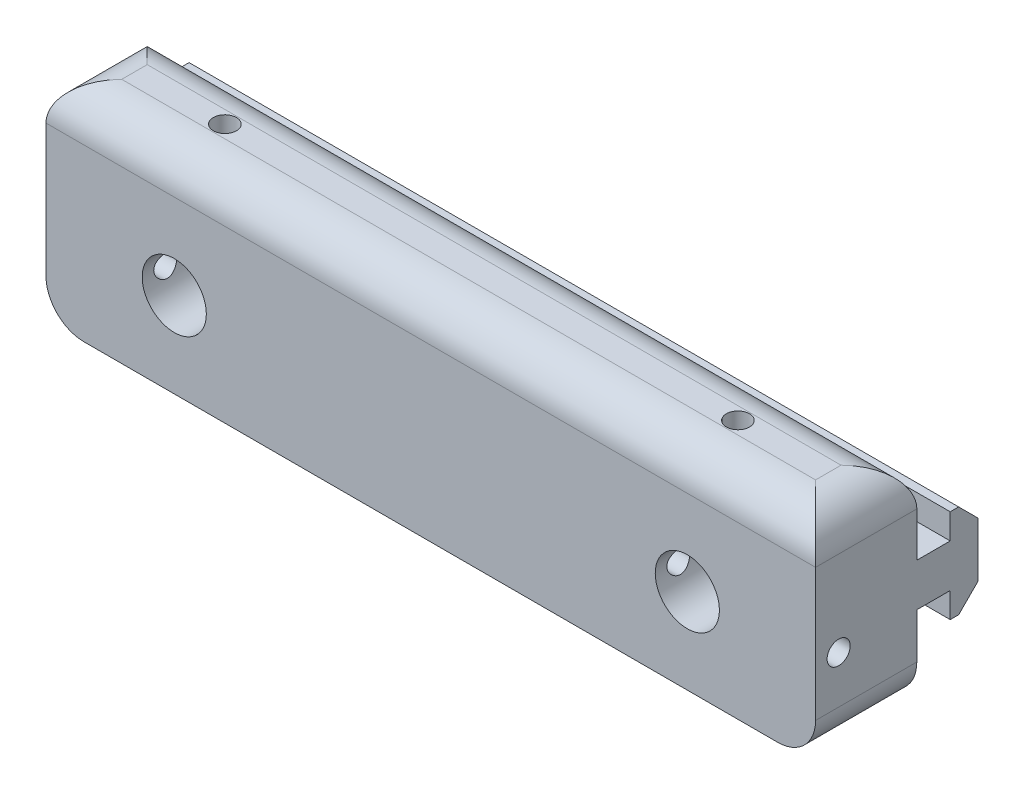
SolidWorks part; units mm, degrees
ref_plane "Front Plane" through (0, 0, 0) normal (0, 0, 1) x (1, 0, 0)
ref_plane "Top Plane" through (0, 0, 0) normal (0, 1, 0) x (1, 0, 0)
ref_plane "Right Plane" through (0, 0, 0) normal (1, 0, 0) x (0, 0, -1)
sketch "Sketch2" plane through (0, 0, 0) normal (1, 0, 0) x (0, 0, -1)
  line L0 (20, -17) -> (20, -5) construction
  line L1 (20, -5) -> (14.5, -5) construction
  line L2 (14.5, -5) -> (14.5, -10) construction
  line L3 (14.5, -10) -> (11.7678, -10) construction
  line L4 (11.7678, -10) -> (7.5, -5.7322) construction
  line L5 (7.5, -5.7322) -> (7.5, -0.5196) construction
  line L6 (7.5, -0.5196) -> (7.2, 0) construction
  line L7 (7.2, 0) -> (7.5, 0.5196) construction
  line L8 (7.5, 0.5196) -> (7.5, 5.7322) construction
  line L9 (7.5, 5.7322) -> (11.7678, 10) construction
  line L10 (11.7678, 10) -> (14.5, 10) construction
  line L11 (14.5, 10) -> (14.5, 5) construction
  line L12 (14.5, 5) -> (20, 5) construction
  line L13 (20, 5) -> (20, 16.9163) construction
  line L14 (17, 19.9163) -> (5, 19.9163) construction
  line L15 (5, 19.9163) -> (5, 14.5) construction
  line L16 (5, 14.5) -> (10, 14.5) construction
  line L17 (10, 14.5) -> (10, 11.7678) construction
  line L18 (10, 11.7678) -> (5.7322, 7.5) construction
  line L19 (5.7322, 7.5) -> (0.5196, 7.5) construction
  line L20 (0.5196, 7.5) -> (0, 7.2) construction
  line L21 (0, 7.2) -> (-0.5196, 7.5) construction
  line L22 (-0.5196, 7.5) -> (-5.7322, 7.5) construction
  line L23 (-5.7322, 7.5) -> (-10, 11.7678) construction
  line L24 (-10, 11.7678) -> (-10, 14.5) construction
  line L25 (-10, 14.5) -> (-5, 14.5) construction
  line L26 (-5, 14.5) -> (-5, 19.9163) construction
  line L27 (-5, 19.9163) -> (-17.0837, 19.9163) construction
  line L28 (-20, 17) -> (-20, 5) construction
  line L29 (-20, 5) -> (-14.5, 5) construction
  line L30 (-14.5, 5) -> (-14.5, 10) construction
  line L31 (-14.5, 10) -> (-11.7678, 10) construction
  line L32 (-11.7678, 10) -> (-7.5, 5.7322) construction
  line L33 (-7.5, 5.7322) -> (-7.5, 0.5196) construction
  line L34 (-7.5, 0.5196) -> (-7.2, 0) construction
  line L35 (-7.2, 0) -> (-7.5, -0.5196) construction
  line L36 (-7.5, -0.5196) -> (-7.5, -5.7322) construction
  line L37 (-7.5, -5.7322) -> (-11.7678, -10) construction
  line L38 (-11.7678, -10) -> (-14.5, -10) construction
  line L39 (-14.5, -10) -> (-14.5, -5) construction
  line L40 (-14.5, -5) -> (-20, -5) construction
  line L41 (-20, -5) -> (-20, -17) construction
  line L42 (-17, -20) -> (17, -20) construction
  line L55 (-21, 3.617) -> (-21, -4.883)
  line L56 (-14.3817, -4.883) -> (-21, -4.883)
  line L57 (-14.3817, -9.883) -> (-14.3817, -4.883)
  line L58 (-12.7101, -9.883) -> (-14.3817, -9.883)
  line L59 (-8.8817, -6.0546) -> (-12.7101, -9.883)
  line L60 (-8.8817, -1.1526) -> (-8.8817, -6.0546)
  line L61 (-8.8817, -0.1134) -> (-8.8817, -1.1526)
  line L62 (-8.8817, 4.7886) -> (-8.8817, -0.1134)
  line L63 (-12.7101, 8.617) -> (-8.8817, 4.7886)
  line L64 (-14.3817, 8.617) -> (-12.7101, 8.617)
  line L65 (-14.3817, 3.617) -> (-14.3817, 8.617)
  line L66 (-21, 3.617) -> (-14.3817, 3.617)
  line L67 (-38.049, -7.3386) -> (-38.049, -11.8386) construction
  line L68 (-37.749, -12.1386) -> (-36.949, -12.1386) construction
  line L69 (-36.949, -12.1386) -> (-36.949, -10.9886) construction
  line L70 (-36.949, -10.9886) -> (-34.349, -10.9886) construction
  line L71 (-34.349, -10.9886) -> (-33.349, -11.9886) construction
  line L72 (-33.349, -11.9886) -> (-33.349, -13.319) construction
  line L73 (-33.349, -13.319) -> (-33.049, -13.8386) construction
  line L74 (-33.049, -13.8386) -> (-33.349, -14.3582) construction
  line L75 (-33.349, -14.3582) -> (-33.349, -15.6886) construction
  line L76 (-33.349, -15.6886) -> (-34.349, -16.6886) construction
  line L77 (-34.349, -16.6886) -> (-36.949, -16.6886) construction
  line L78 (-36.949, -16.6886) -> (-36.949, -15.5386) construction
  line L79 (-36.949, -15.5386) -> (-37.749, -15.5386) construction
  line L80 (-38.049, -15.8386) -> (-38.049, -20.3386) construction
  line L81 (-37.049, -21.3386) -> (-32.549, -21.3386) construction
  line L82 (-32.249, -21.0386) -> (-32.249, -20.2386) construction
  line L83 (-32.249, -20.2386) -> (-33.399, -20.2386) construction
  line L84 (-33.399, -20.2386) -> (-33.399, -17.6386) construction
  line L85 (-33.399, -17.6386) -> (-32.399, -16.6386) construction
  line L86 (-32.399, -16.6386) -> (-31.0686, -16.6386) construction
  line L87 (-31.0686, -16.6386) -> (-30.549, -16.3386) construction
  line L88 (-30.549, -16.3386) -> (-30.0293, -16.6386) construction
  line L89 (-30.0293, -16.6386) -> (-28.699, -16.6386) construction
  line L90 (-28.699, -16.6386) -> (-27.699, -17.6386) construction
  line L91 (-27.699, -17.6386) -> (-27.699, -20.2386) construction
  line L92 (-27.699, -20.2386) -> (-28.849, -20.2386) construction
  line L93 (-28.849, -20.2386) -> (-28.849, -21.0386) construction
  line L94 (-28.549, -21.3386) -> (-24.049, -21.3386) construction
  line L95 (-23.049, -20.3386) -> (-23.049, -15.8386) construction
  line L96 (-23.349, -15.5386) -> (-24.149, -15.5386) construction
  line L97 (-24.149, -15.5386) -> (-24.149, -16.6886) construction
  line L98 (-24.149, -16.6886) -> (-26.749, -16.6886) construction
  line L99 (-26.749, -16.6886) -> (-27.749, -15.6886) construction
  line L100 (-27.749, -15.6886) -> (-27.749, -14.3582) construction
  line L101 (-27.749, -14.3582) -> (-28.049, -13.8386) construction
  line L102 (-28.049, -13.8386) -> (-27.749, -13.319) construction
  line L103 (-27.749, -13.319) -> (-27.749, -11.9886) construction
  line L104 (-27.749, -11.9886) -> (-26.749, -10.9886) construction
  line L105 (-26.749, -10.9886) -> (-24.149, -10.9886) construction
  line L106 (-24.149, -10.9886) -> (-24.149, -12.1386) construction
  line L107 (-24.149, -12.1386) -> (-23.349, -12.1386) construction
  line L108 (-23.049, -11.8386) -> (-23.049, -7.3386) construction
  line L109 (-24.049, -6.3386) -> (-28.549, -6.3386) construction
  line L110 (-28.849, -6.6386) -> (-28.849, -7.4386) construction
  line L111 (-28.849, -7.4386) -> (-27.699, -7.4386) construction
  line L112 (-27.699, -7.4386) -> (-27.699, -10.0386) construction
  line L113 (-27.699, -10.0386) -> (-28.699, -11.0386) construction
  line L114 (-28.699, -11.0386) -> (-30.0293, -11.0386) construction
  line L115 (-30.0293, -11.0386) -> (-30.549, -11.3386) construction
  line L116 (-30.549, -11.3386) -> (-31.0686, -11.0386) construction
  line L117 (-31.0686, -11.0386) -> (-32.399, -11.0386) construction
  line L118 (-32.399, -11.0386) -> (-33.399, -10.0386) construction
  line L119 (-33.399, -10.0386) -> (-33.399, -7.4386) construction
  line L120 (-33.399, -7.4386) -> (-32.249, -7.4386) construction
  line L121 (-32.249, -7.4386) -> (-32.249, -6.6386) construction
  line L122 (-32.549, -6.3386) -> (-37.049, -6.3386) construction
  line L123 (-37.049, -6.3386) -> (-41.049, -6.3386) construction
  line L124 (-24.049, -6.3386) -> (-20.049, -6.3386) construction
  line L125 (-21, 3.617) -> (-21, 19.9163)
  line L126 (-21, 19.9163) -> (-41.049, 19.9163)
  line L127 (-41.049, 19.9163) -> (-41.049, -21.3386)
  line L128 (-41.049, -21.3386) -> (-21, -21.3386)
  line L129 (-21, -21.3386) -> (-21, -5)
  line L130 (-21, -5) -> (-21, 3.617)
  arc A0 (20, 16.9163) -> (17, 19.9163) centre (17, 16.9163) ccw construction
  arc A1 (-17.0837, 19.9163) -> (-20, 17) centre (-17.0837, 17) ccw construction
  arc A2 (-20, -17) -> (-17, -20) centre (-17, -17) ccw construction
  arc A3 (17, -20) -> (20, -17) centre (17, -17) ccw construction
  circle A4 centre (-30.549, -13.8386) radius 1.25 construction
  arc A5 (-38.049, -11.8386) -> (-37.749, -12.1386) centre (-37.749, -11.8386) ccw construction
  arc A6 (-37.749, -15.5386) -> (-38.049, -15.8386) centre (-37.749, -15.8386) ccw construction
  arc A7 (-38.049, -20.3386) -> (-37.049, -21.3386) centre (-37.049, -20.3386) ccw construction
  arc A8 (-32.549, -21.3386) -> (-32.249, -21.0386) centre (-32.549, -21.0386) ccw construction
  arc A9 (-28.849, -21.0386) -> (-28.549, -21.3386) centre (-28.549, -21.0386) ccw construction
  arc A10 (-24.049, -21.3386) -> (-23.049, -20.3386) centre (-24.049, -20.3386) ccw construction
  arc A11 (-23.049, -15.8386) -> (-23.349, -15.5386) centre (-23.349, -15.8386) ccw construction
  arc A12 (-23.349, -12.1386) -> (-23.049, -11.8386) centre (-23.349, -11.8386) ccw construction
  arc A13 (-23.049, -7.3386) -> (-24.049, -6.3386) centre (-24.049, -7.3386) ccw construction
  arc A14 (-28.549, -6.3386) -> (-28.849, -6.6386) centre (-28.549, -6.6386) ccw construction
  arc A15 (-32.249, -6.6386) -> (-32.549, -6.3386) centre (-32.549, -6.6386) ccw construction
  arc A16 (-37.049, -6.3386) -> (-38.049, -7.3386) centre (-37.049, -7.3386) ccw construction
extrude "Boss-Extrude2" add sketch "Sketch2" along normal blind 152.4 contours L129 L130 L55 L125 L126 L127 L128 | L66 L55 L56 L57 L58 L59 L60 L61 L62 L63 L64 L65 region at (0, -0.633, 14.1602) region at (0, -0.7111, 31.0245)
sketch "Sketch3" plane through (0, -21.3386, 0) normal (0, -1, 0) x (1, 0, 0)
  line L56 (56, 37.5197) -> (56, 33.0197) construction
  line L59 (88.9, 41.049) -> (88.9, 21) construction
  line L60 (56.3, 32.7197) -> (57.1, 32.7197) construction
  line L61 (90.9, 38.5197) -> (95.4, 38.5197) construction
  line L62 (57.1, 32.7197) -> (57.1, 33.8697) construction
  line L117 (57.1, 33.8697) -> (59.7, 33.8697) construction
  line L119 (90.6, 37.4197) -> (90.6, 38.2197) construction
  line L120 (59.7, 33.8697) -> (60.7, 32.8697) construction
  line L121 (91.75, 37.4197) -> (90.6, 37.4197) construction
  line L122 (60.7, 32.8697) -> (60.7, 31.5393) construction
  line L290 (60.7, 31.5393) -> (61, 31.0197) construction
  line L291 (61, 31.0197) -> (60.7, 30.5001) construction
  line L292 (60.7, 30.5001) -> (60.7, 29.1697) construction
  line L293 (60.7, 29.1697) -> (59.7, 28.1697) construction
  line L294 (59.7, 28.1697) -> (57.1, 28.1697) construction
  line L295 (57.1, 28.1697) -> (57.1, 29.3197) construction
  line L296 (57.1, 29.3197) -> (56.3, 29.3197) construction
  line L297 (56, 29.0197) -> (56, 24.5197) construction
  line L298 (57, 23.5197) -> (61.5, 23.5197) construction
  line L299 (61.8, 23.8197) -> (61.8, 24.6197) construction
  line L300 (61.8, 24.6197) -> (60.65, 24.6197) construction
  line L301 (60.65, 24.6197) -> (60.65, 27.2197) construction
  line L302 (60.65, 27.2197) -> (61.65, 28.2197) construction
  line L303 (61.65, 28.2197) -> (62.9804, 28.2197) construction
  line L304 (62.9804, 28.2197) -> (63.5, 28.5197) construction
  line L305 (63.5, 28.5197) -> (64.0196, 28.2197) construction
  line L306 (64.0196, 28.2197) -> (65.35, 28.2197) construction
  line L307 (65.35, 28.2197) -> (66.35, 27.2197) construction
  line L308 (66.35, 27.2197) -> (66.35, 24.6197) construction
  line L309 (66.35, 24.6197) -> (65.2, 24.6197) construction
  line L310 (65.2, 24.6197) -> (65.2, 23.8197) construction
  line L311 (65.5, 23.5197) -> (70, 23.5197) construction
  line L312 (71, 24.5197) -> (71, 29.0197) construction
  line L313 (70.7, 29.3197) -> (69.9, 29.3197) construction
  line L314 (69.9, 29.3197) -> (69.9, 28.1697) construction
  line L315 (69.9, 28.1697) -> (67.3, 28.1697) construction
  line L316 (67.3, 28.1697) -> (66.3, 29.1697) construction
  line L317 (66.3, 29.1697) -> (66.3, 30.5001) construction
  line L318 (66.3, 30.5001) -> (66, 31.0197) construction
  line L319 (66, 31.0197) -> (66.3, 31.5393) construction
  line L320 (66.3, 31.5393) -> (66.3, 32.8697) construction
  line L321 (66.3, 32.8697) -> (67.3, 33.8697) construction
  line L322 (67.3, 33.8697) -> (69.9, 33.8697) construction
  line L323 (69.9, 33.8697) -> (69.9, 32.7197) construction
  line L324 (69.9, 32.7197) -> (70.7, 32.7197) construction
  line L325 (71, 33.0197) -> (71, 37.5197) construction
  line L326 (70, 38.5197) -> (65.5, 38.5197) construction
  line L327 (65.2, 38.2197) -> (65.2, 37.4197) construction
  line L328 (65.2, 37.4197) -> (66.35, 37.4197) construction
  line L329 (66.35, 37.4197) -> (66.35, 34.8197) construction
  line L330 (66.35, 34.8197) -> (65.35, 33.8197) construction
  line L331 (65.35, 33.8197) -> (64.0196, 33.8197) construction
  line L332 (64.0196, 33.8197) -> (63.5, 33.5197) construction
  line L333 (63.5, 33.5197) -> (62.9804, 33.8197) construction
  line L334 (62.9804, 33.8197) -> (61.65, 33.8197) construction
  line L335 (61.65, 33.8197) -> (60.65, 34.8197) construction
  line L336 (60.65, 34.8197) -> (60.65, 37.4197) construction
  line L337 (60.65, 37.4197) -> (61.8, 37.4197) construction
  line L338 (61.8, 37.4197) -> (61.8, 38.2197) construction
  line L339 (61.5, 38.5197) -> (57, 38.5197) construction
  line L340 (55.5, 37.4686) -> (55.5, 32.9686)
  line L341 (56.3, 32.1686) -> (57.6, 32.1686)
  line L342 (57.6, 32.1686) -> (57.6, 33.3186)
  line L343 (57.6, 33.3186) -> (59.4929, 33.3186)
  line L344 (59.4929, 33.3186) -> (60.2, 32.6115)
  line L345 (60.2, 32.6115) -> (60.2, 31.3542)
  line L346 (60.2, 31.3542) -> (60.4226, 30.9686)
  line L347 (60.4226, 30.9686) -> (60.2, 30.5829)
  line L348 (60.2, 30.5829) -> (60.2, 29.3257)
  line L349 (60.2, 29.3257) -> (59.4929, 28.6186)
  line L350 (59.4929, 28.6186) -> (57.6, 28.6186)
  line L351 (57.6, 28.6186) -> (57.6, 29.7686)
  line L352 (57.6, 29.7686) -> (56.3, 29.7686)
  line L353 (55.5, 28.9686) -> (55.5, 24.4686)
  line L354 (57, 22.9686) -> (61.5, 22.9686)
  line L355 (62.3, 23.7686) -> (62.3, 25.0686)
  line L356 (62.3, 25.0686) -> (61.15, 25.0686)
  line L357 (61.15, 25.0686) -> (61.15, 26.9615)
  line L358 (61.15, 26.9615) -> (61.8571, 27.6686)
  line L359 (61.8571, 27.6686) -> (63.1144, 27.6686)
  line L360 (63.1144, 27.6686) -> (63.5, 27.8912)
  line L361 (63.5, 27.8912) -> (63.8856, 27.6686)
  line L362 (63.8856, 27.6686) -> (65.1429, 27.6686)
  line L363 (65.1429, 27.6686) -> (65.85, 26.9615)
  line L364 (65.85, 26.9615) -> (65.85, 25.0686)
  line L365 (65.85, 25.0686) -> (64.7, 25.0686)
  line L366 (64.7, 25.0686) -> (64.7, 23.7686)
  line L367 (65.5, 22.9686) -> (70, 22.9686)
  line L368 (71.5, 24.4686) -> (71.5, 28.9686)
  line L369 (70.7, 29.7686) -> (69.4, 29.7686)
  line L370 (69.4, 29.7686) -> (69.4, 28.6186)
  line L371 (69.4, 28.6186) -> (67.5071, 28.6186)
  line L372 (67.5071, 28.6186) -> (66.8, 29.3257)
  line L373 (66.8, 29.3257) -> (66.8, 30.5829)
  line L374 (66.8, 30.5829) -> (66.5774, 30.9686)
  line L375 (66.5774, 30.9686) -> (66.8, 31.3542)
  line L376 (66.8, 31.3542) -> (66.8, 32.6115)
  line L377 (66.8, 32.6115) -> (67.5071, 33.3186)
  line L378 (67.5071, 33.3186) -> (69.4, 33.3186)
  line L379 (69.4, 33.3186) -> (69.4, 32.1686)
  line L380 (69.4, 32.1686) -> (70.7, 32.1686)
  line L381 (71.5, 32.9686) -> (71.5, 37.4686)
  line L382 (70, 38.9686) -> (65.5, 38.9686)
  line L383 (64.7, 38.1686) -> (64.7, 36.8686)
  line L384 (64.7, 36.8686) -> (65.85, 36.8686)
  line L385 (65.85, 36.8686) -> (65.85, 34.9757)
  line L386 (65.85, 34.9757) -> (65.1429, 34.2686)
  line L387 (65.1429, 34.2686) -> (63.8856, 34.2686)
  line L388 (63.8856, 34.2686) -> (63.5, 34.0459)
  line L389 (63.5, 34.0459) -> (63.1144, 34.2686)
  line L390 (63.1144, 34.2686) -> (61.8571, 34.2686)
  line L391 (61.8571, 34.2686) -> (61.15, 34.9757)
  line L392 (61.15, 34.9757) -> (61.15, 36.8686)
  line L393 (61.15, 36.8686) -> (62.3, 36.8686)
  line L394 (62.3, 36.8686) -> (62.3, 38.1686)
  line L395 (61.5, 38.9686) -> (57, 38.9686)
  line L396 (0, 31.0245) -> (152.4, 31.0245) construction
  line L397 (0, 41.049) -> (0, 21) construction
  line L398 (152.4, 41.049) -> (152.4, 21) construction
  line L399 (76.2, 21) -> (76.2, 41.049) construction
  line L400 (152.4, 21) -> (0, 21) construction
  line L401 (152.4, 41.049) -> (0, 41.049) construction
  line L402 (76.2, 41.049) -> (63.5, 41.049) construction
  line L403 (63.5, 41.049) -> (63.5, 21) construction
  line L404 (91.75, 34.8197) -> (91.75, 37.4197) construction
  line L405 (90.75, 33.8197) -> (91.75, 34.8197) construction
  line L406 (89.4196, 33.8197) -> (90.75, 33.8197) construction
  line L407 (88.9, 33.5197) -> (89.4196, 33.8197) construction
  line L408 (88.3804, 33.8197) -> (88.9, 33.5197) construction
  line L409 (87.05, 33.8197) -> (88.3804, 33.8197) construction
  line L410 (86.05, 34.8197) -> (87.05, 33.8197) construction
  line L411 (86.05, 37.4197) -> (86.05, 34.8197) construction
  line L412 (87.2, 37.4197) -> (86.05, 37.4197) construction
  line L413 (87.2, 38.2197) -> (87.2, 37.4197) construction
  line L414 (82.4, 38.5197) -> (86.9, 38.5197) construction
  line L415 (81.4, 33.0197) -> (81.4, 37.5197) construction
  line L416 (82.5, 32.7197) -> (81.7, 32.7197) construction
  line L417 (82.5, 33.8697) -> (82.5, 32.7197) construction
  line L418 (85.1, 33.8697) -> (82.5, 33.8697) construction
  line L419 (86.1, 32.8697) -> (85.1, 33.8697) construction
  line L420 (86.1, 31.5393) -> (86.1, 32.8697) construction
  line L421 (86.4, 31.0197) -> (86.1, 31.5393) construction
  line L422 (86.1, 30.5001) -> (86.4, 31.0197) construction
  line L423 (86.1, 29.1697) -> (86.1, 30.5001) construction
  line L424 (85.1, 28.1697) -> (86.1, 29.1697) construction
  line L425 (82.5, 28.1697) -> (85.1, 28.1697) construction
  line L426 (82.5, 29.3197) -> (82.5, 28.1697) construction
  line L427 (81.7, 29.3197) -> (82.5, 29.3197) construction
  line L428 (81.4, 24.5197) -> (81.4, 29.0197) construction
  line L429 (86.9, 23.5197) -> (82.4, 23.5197) construction
  line L430 (87.2, 24.6197) -> (87.2, 23.8197) construction
  line L431 (86.05, 24.6197) -> (87.2, 24.6197) construction
  line L432 (86.05, 27.2197) -> (86.05, 24.6197) construction
  line L433 (87.05, 28.2197) -> (86.05, 27.2197) construction
  line L434 (88.3804, 28.2197) -> (87.05, 28.2197) construction
  line L435 (88.9, 28.5197) -> (88.3804, 28.2197) construction
  line L436 (89.4196, 28.2197) -> (88.9, 28.5197) construction
  line L437 (90.75, 28.2197) -> (89.4196, 28.2197) construction
  line L438 (91.75, 27.2197) -> (90.75, 28.2197) construction
  line L439 (91.75, 24.6197) -> (91.75, 27.2197) construction
  line L440 (90.6, 24.6197) -> (91.75, 24.6197) construction
  line L441 (90.6, 23.8197) -> (90.6, 24.6197) construction
  line L442 (95.4, 23.5197) -> (90.9, 23.5197) construction
  line L443 (96.4, 29.0197) -> (96.4, 24.5197) construction
  line L444 (95.3, 29.3197) -> (96.1, 29.3197) construction
  line L445 (95.3, 28.1697) -> (95.3, 29.3197) construction
  line L446 (92.7, 28.1697) -> (95.3, 28.1697) construction
  line L447 (91.7, 29.1697) -> (92.7, 28.1697) construction
  line L448 (91.7, 30.5001) -> (91.7, 29.1697) construction
  line L449 (91.4, 31.0197) -> (91.7, 30.5001) construction
  line L450 (91.7, 31.5393) -> (91.4, 31.0197) construction
  line L451 (91.7, 32.8697) -> (91.7, 31.5393) construction
  line L452 (92.7, 33.8697) -> (91.7, 32.8697) construction
  line L453 (95.3, 33.8697) -> (92.7, 33.8697) construction
  line L454 (95.3, 32.7197) -> (95.3, 33.8697) construction
  line L455 (96.1, 32.7197) -> (95.3, 32.7197) construction
  line L456 (96.4, 37.5197) -> (96.4, 33.0197) construction
  line L457 (90.9, 38.9686) -> (95.4, 38.9686)
  line L458 (90.1, 36.8686) -> (90.1, 38.1686)
  line L459 (91.25, 36.8686) -> (90.1, 36.8686)
  line L460 (91.25, 34.9757) -> (91.25, 36.8686)
  line L461 (90.5429, 34.2686) -> (91.25, 34.9757)
  line L462 (89.2856, 34.2686) -> (90.5429, 34.2686)
  line L463 (88.9, 34.0459) -> (89.2856, 34.2686)
  line L464 (88.5144, 34.2686) -> (88.9, 34.0459)
  line L465 (87.2571, 34.2686) -> (88.5144, 34.2686)
  line L466 (86.55, 34.9757) -> (87.2571, 34.2686)
  line L467 (86.55, 36.8686) -> (86.55, 34.9757)
  line L468 (87.7, 36.8686) -> (86.55, 36.8686)
  line L469 (87.7, 38.1686) -> (87.7, 36.8686)
  line L470 (82.4, 38.9686) -> (86.9, 38.9686)
  line L471 (80.9, 32.9686) -> (80.9, 37.4686)
  line L472 (83, 32.1686) -> (81.7, 32.1686)
  line L473 (83, 33.3186) -> (83, 32.1686)
  line L474 (84.8929, 33.3186) -> (83, 33.3186)
  line L475 (85.6, 32.6115) -> (84.8929, 33.3186)
  line L476 (85.6, 31.3542) -> (85.6, 32.6115)
  line L477 (85.8226, 30.9686) -> (85.6, 31.3542)
  line L478 (85.6, 30.5829) -> (85.8226, 30.9686)
  line L479 (85.6, 29.3257) -> (85.6, 30.5829)
  line L480 (84.8929, 28.6186) -> (85.6, 29.3257)
  line L481 (83, 28.6186) -> (84.8929, 28.6186)
  line L482 (83, 29.7686) -> (83, 28.6186)
  line L483 (81.7, 29.7686) -> (83, 29.7686)
  line L484 (80.9, 24.4686) -> (80.9, 28.9686)
  line L485 (86.9, 22.9686) -> (82.4, 22.9686)
  line L486 (87.7, 25.0686) -> (87.7, 23.7686)
  line L487 (86.55, 25.0686) -> (87.7, 25.0686)
  line L488 (86.55, 26.9615) -> (86.55, 25.0686)
  line L489 (87.2571, 27.6686) -> (86.55, 26.9615)
  line L490 (88.5144, 27.6686) -> (87.2571, 27.6686)
  line L491 (88.9, 27.8912) -> (88.5144, 27.6686)
  line L492 (89.2856, 27.6686) -> (88.9, 27.8912)
  line L493 (90.5429, 27.6686) -> (89.2856, 27.6686)
  line L494 (91.25, 26.9615) -> (90.5429, 27.6686)
  line L495 (91.25, 25.0686) -> (91.25, 26.9615)
  line L496 (90.1, 25.0686) -> (91.25, 25.0686)
  line L497 (90.1, 23.7686) -> (90.1, 25.0686)
  line L498 (95.4, 22.9686) -> (90.9, 22.9686)
  line L499 (96.9, 28.9686) -> (96.9, 24.4686)
  line L500 (94.8, 29.7686) -> (96.1, 29.7686)
  line L501 (94.8, 28.6186) -> (94.8, 29.7686)
  line L502 (92.9071, 28.6186) -> (94.8, 28.6186)
  line L503 (92.2, 29.3257) -> (92.9071, 28.6186)
  line L504 (92.2, 30.5829) -> (92.2, 29.3257)
  line L505 (91.9774, 30.9686) -> (92.2, 30.5829)
  line L506 (92.2, 31.3542) -> (91.9774, 30.9686)
  line L507 (92.2, 32.6115) -> (92.2, 31.3542)
  line L508 (92.9071, 33.3186) -> (92.2, 32.6115)
  line L509 (94.8, 33.3186) -> (92.9071, 33.3186)
  line L510 (94.8, 32.1686) -> (94.8, 33.3186)
  line L511 (96.1, 32.1686) -> (94.8, 32.1686)
  line L512 (96.9, 37.4686) -> (96.9, 32.9686)
  arc A61 (56, 33.0197) -> (56.3, 32.7197) centre (56.3, 33.0197) ccw construction
  arc A62 (56.3, 29.3197) -> (56, 29.0197) centre (56.3, 29.0197) ccw construction
  arc A63 (56, 24.5197) -> (57, 23.5197) centre (57, 24.5197) ccw construction
  arc A64 (61.5, 23.5197) -> (61.8, 23.8197) centre (61.5, 23.8197) ccw construction
  arc A65 (65.2, 23.8197) -> (65.5, 23.5197) centre (65.5, 23.8197) ccw construction
  arc A66 (70, 23.5197) -> (71, 24.5197) centre (70, 24.5197) ccw construction
  arc A67 (71, 29.0197) -> (70.7, 29.3197) centre (70.7, 29.0197) ccw construction
  arc A68 (70.7, 32.7197) -> (71, 33.0197) centre (70.7, 33.0197) ccw construction
  arc A69 (71, 37.5197) -> (70, 38.5197) centre (70, 37.5197) ccw construction
  arc A70 (65.5, 38.5197) -> (65.2, 38.2197) centre (65.5, 38.2197) ccw construction
  arc A71 (61.8, 38.2197) -> (61.5, 38.5197) centre (61.5, 38.2197) ccw construction
  arc A72 (57, 38.5197) -> (56, 37.5197) centre (57, 37.5197) ccw construction
  arc A73 (55.5, 32.9686) -> (56.3, 32.1686) centre (56.3, 32.9686) ccw
  arc A74 (56.3, 29.7686) -> (55.5, 28.9686) centre (56.3, 28.9686) ccw
  arc A75 (55.5, 24.4686) -> (57, 22.9686) centre (57, 24.4686) ccw
  arc A76 (61.5, 22.9686) -> (62.3, 23.7686) centre (61.5, 23.7686) ccw
  arc A77 (64.7, 23.7686) -> (65.5, 22.9686) centre (65.5, 23.7686) ccw
  arc A78 (70, 22.9686) -> (71.5, 24.4686) centre (70, 24.4686) ccw
  arc A79 (71.5, 28.9686) -> (70.7, 29.7686) centre (70.7, 28.9686) ccw
  arc A80 (70.7, 32.1686) -> (71.5, 32.9686) centre (70.7, 32.9686) ccw
  arc A81 (71.5, 37.4686) -> (70, 38.9686) centre (70, 37.4686) ccw
  arc A82 (65.5, 38.9686) -> (64.7, 38.1686) centre (65.5, 38.1686) ccw
  arc A83 (62.3, 38.1686) -> (61.5, 38.9686) centre (61.5, 38.1686) ccw
  arc A84 (57, 38.9686) -> (55.5, 37.4686) centre (57, 37.4686) ccw
  arc A85 (95.4, 38.5197) -> (96.4, 37.5197) centre (95.4, 37.5197) cw construction
  arc A86 (90.6, 38.2197) -> (90.9, 38.5197) centre (90.9, 38.2197) cw construction
  arc A87 (86.9, 38.5197) -> (87.2, 38.2197) centre (86.9, 38.2197) cw construction
  arc A88 (81.4, 37.5197) -> (82.4, 38.5197) centre (82.4, 37.5197) cw construction
  arc A89 (81.7, 32.7197) -> (81.4, 33.0197) centre (81.7, 33.0197) cw construction
  arc A90 (81.4, 29.0197) -> (81.7, 29.3197) centre (81.7, 29.0197) cw construction
  arc A91 (82.4, 23.5197) -> (81.4, 24.5197) centre (82.4, 24.5197) cw construction
  arc A92 (87.2, 23.8197) -> (86.9, 23.5197) centre (86.9, 23.8197) cw construction
  arc A93 (90.9, 23.5197) -> (90.6, 23.8197) centre (90.9, 23.8197) cw construction
  arc A94 (96.4, 24.5197) -> (95.4, 23.5197) centre (95.4, 24.5197) cw construction
  arc A95 (96.1, 29.3197) -> (96.4, 29.0197) centre (96.1, 29.0197) cw construction
  arc A96 (96.4, 33.0197) -> (96.1, 32.7197) centre (96.1, 33.0197) cw construction
  arc A97 (95.4, 38.9686) -> (96.9, 37.4686) centre (95.4, 37.4686) cw
  arc A98 (90.1, 38.1686) -> (90.9, 38.9686) centre (90.9, 38.1686) cw
  arc A99 (86.9, 38.9686) -> (87.7, 38.1686) centre (86.9, 38.1686) cw
  arc A100 (80.9, 37.4686) -> (82.4, 38.9686) centre (82.4, 37.4686) cw
  arc A101 (81.7, 32.1686) -> (80.9, 32.9686) centre (81.7, 32.9686) cw
  arc A102 (80.9, 28.9686) -> (81.7, 29.7686) centre (81.7, 28.9686) cw
  arc A103 (82.4, 22.9686) -> (80.9, 24.4686) centre (82.4, 24.4686) cw
  arc A104 (87.7, 23.7686) -> (86.9, 22.9686) centre (86.9, 23.7686) cw
  arc A105 (90.9, 22.9686) -> (90.1, 23.7686) centre (90.9, 23.7686) cw
  arc A106 (96.9, 24.4686) -> (95.4, 22.9686) centre (95.4, 24.4686) cw
  arc A107 (96.1, 29.7686) -> (96.9, 28.9686) centre (96.1, 28.9686) cw
  arc A108 (96.9, 32.9686) -> (96.1, 32.1686) centre (96.1, 32.9686) cw
extrude "Cut-Extrude1" cut sketch "Sketch3" against normal blind 25.4 contours A98 L457 A97 L512 A108 L511 L510 L509 L508 L507 L506 L505 L504 L503 L502 L501 L500 A107 L499 A106 L498 A105 L497 L496 L495 L494 L493 L492 L491 L490 L489 L488 L487 L486 A104 L485 A103 L484 A102 L483 L482 L481 L480 L479 L478 L477 L476 L475 L474 L473 L472 A101 L471 A100 L470 A99 L469 L468 L467 L466 L465 L464 L463 L462 L461 L460 L459 L458 | L340 A73 L341 L342 L343 L344 L345 L346 L347 L348 L349 L350 L351 L352 A74 L353 A75 L354 A76 L355 L356 L357 L358 L359 L360 L361 L362 L363 L364 L365 L366 A77 L367 A78 L368 A79 L369 L370 L371 L372 L373 L374 L375 L376 L377 L378 L379 L380 A80 L381 A81 L382 A82 L383 L384 L385 L386 L387 L388 L389 L390 L391 L392 L393 L394 A83 L395 A84
fillet "Fillet1" radius 7.5 6 edges at (0, -21.3386, 31.0245) (152.4, -21.3386, 31.0245) (152.4, 19.9163, 31.0245) (76.2, 19.9163, 41.049) (0, 19.9163, 31.0245) (76.2, 19.9163, 21)
sketch "Sketch4" plane through (0, -21.3386, 0) normal (0, -1, 0) x (1, 0, 0)
  line L0 (76.2, 21) -> (76.2, 41.049) construction
  line L1 (152.4, 21) -> (0, 21) construction
  line L2 (144.9, 41.049) -> (7.5, 41.049) construction
  line L3 (76.2, 31.0245) -> (25.4, 31.0245) construction
  circle A0 centre (25.4, 31.0245) radius 2.286
  circle A1 centre (127, 31.0245) radius 2.286
extrude "Cut-Extrude2" cut sketch "Sketch4" against normal blind 48.26
sketch "Sketch5" plane through (0, 0, 41.049) normal (0, 0, 1) x (1, 0, 0)
  line L0 (76.2, 12.4163) -> (76.2, -21.3386) construction
  line L1 (152.4, 12.4163) -> (0, 12.4163) construction
  line L2 (144.9, -21.3386) -> (7.5, -21.3386) construction
  line L3 (76.2, -4.4611) -> (25.4, -4.4611) construction
  line L4 (25.4, -4.4611) -> (0, -4.4611) construction
  line L5 (0, 12.4163) -> (0, -13.8386) construction
  line L6 (0, -4.4611) -> (0, -21.3386) construction
  circle A0 centre (25.4, -4.4611) radius 6.35
  circle A1 centre (127, -4.4611) radius 6.35
extrude "Cut-Extrude3" cut sketch "Sketch5" against normal blind 12.7 contours A1 | A0
sketch "Sketch7" plane through (0, 0, 0) normal (-1, 0, 0) x (0, 0, 1)
  line L0 (39.4723, -21.3386) -> (39.4723, -4.4611) construction
  line L1 (41.049, -21.3386) -> (21, -21.3386) construction
  line L2 (41.049, -4.4611) -> (36.477, -4.4611) construction
  line L3 (41.049, 12.4163) -> (41.049, -13.8386) construction
  circle A0 centre (36.477, -4.4611) radius 2.286
extrude "Cut-Extrude4" cut sketch "Sketch7" against normal blind 50.8
sketch "Sketch8" plane through (152.4, 0, 0) normal (1, 0, 0) x (0, 0, -1)
  line L0 (-39.4723, -21.3386) -> (-39.4723, -4.4611) construction
  line L1 (-35.9838, -21.3386) -> (-41.049, -21.3386) construction
  line L2 (-41.049, -4.4611) -> (-36.477, -4.4611) construction
  line L3 (-21, -21.3386) -> (-41.049, -21.3386) construction
  line L4 (-41.049, -3.2735) -> (-41.049, -21.3386) construction
  line L5 (-41.049, 12.4163) -> (-41.049, -13.8386) construction
  circle A1 centre (-36.477, -4.4611) radius 2.286
extrude "Cut-Extrude5" cut sketch "Sketch8" against normal blind 50.8 contours A1
